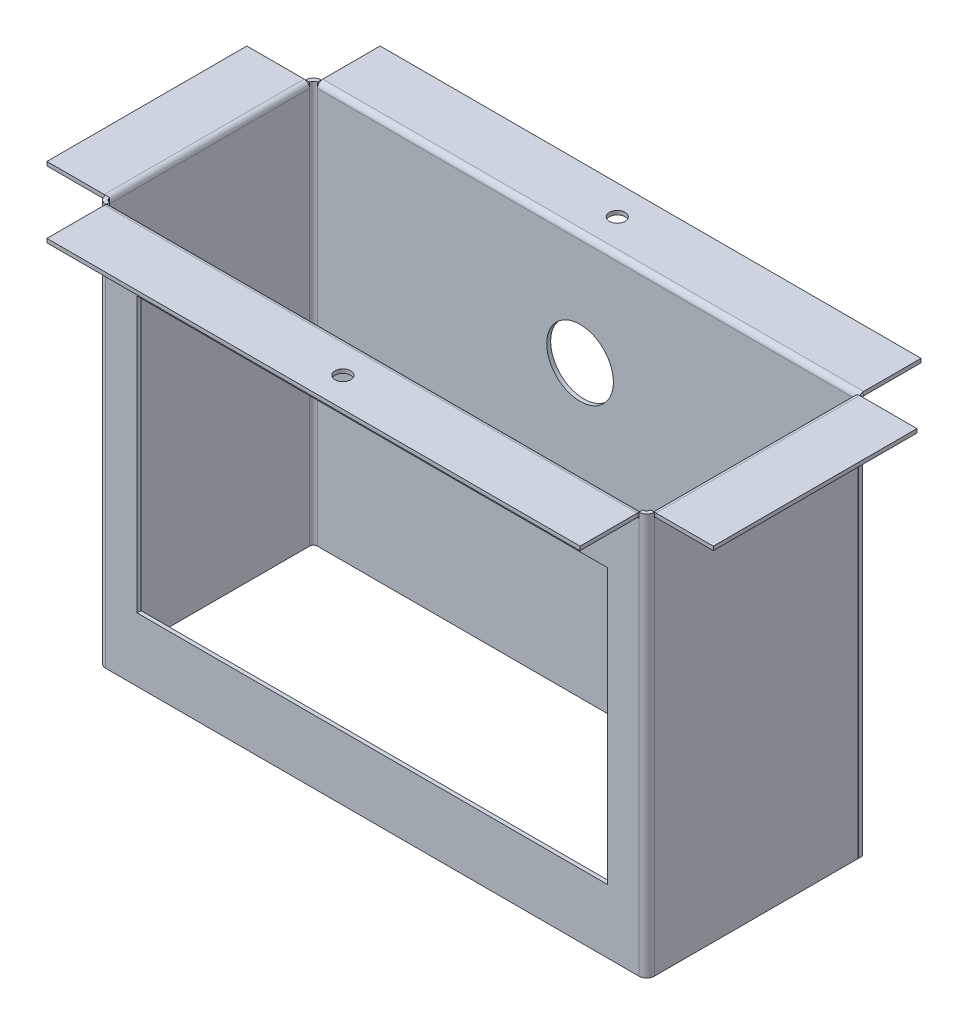
SolidWorks part; units mm, degrees
note: The reader was unsure of these and kept them because the rebuilt part matched: flange length of "Edge-Flange1", "Edge-Flange2", "Edge-Flange3", "Edge-Flange11".
material "Galvanized Steel"
ref_plane "Front Plane" through (0, 0, 0) normal (0, 0, 1) x (1, 0, 0)
ref_plane "Top Plane" through (0, 0, 0) normal (0, 1, 0) x (1, 0, 0)
ref_plane "Right Plane" through (0, 0, 0) normal (1, 0, 0) x (0, 0, -1)
sketch "Sketch1" plane through (0, 0, 0) normal (0, 0, 1) x (1, 0, 0)
  line L1 (44.0222, 46.0111) -> (-235.9778, 46.0111)
  line L2 (44.0222, 46.0111) -> (44.0222, -158.9889)
  line L3 (44.0222, -158.9889) -> (-235.9778, -158.9889)
  line L4 (-235.9778, 46.0111) -> (-235.9778, -158.9889)
  dimension "D1" = 205
  dimension "D2" = 280
base flange "Base-Flange1" sketch "Sketch1" thickness 2 reverse thickness direction no parameters "D1"=0.7366
edge flange "Edge-Flange1" sketch "Sketch8" flange angle 90 flange length 110 flange position material inside bend radius 2 thickness 2 relief obround parameters "D6"=10
sketch "Sketch8" plane through (-235.9778, 0, 0) normal (1, 0, 0) x (0, 1, 0)
  line L2 (-158.9889, 0) -> (-158.9889, 108)
  line L3 (-158.9889, 108) -> (46.0111, 108)
  line L4 (46.0111, 108) -> (46.0111, 0)
  line L6 (46.0111, 0) -> (-158.9889, 0) construction
  line L7 (46.0111, 0) -> (-158.9889, 0)
bend "EdgeBend1" bend radius 2 bend angle 90 parameters "D5"=1
edge flange "Edge-Flange2" sketch "Sketch11" flange angle 90 flange length 280 flange position material inside bend radius 2 thickness 2 relief obround parameters "D6"=10
sketch "Sketch11" plane through (-233.9778, 0, 108) normal (0, 0, -1) x (0, 1, 0)
  line L1 (46.0111, 0) -> (-158.9889, 0) construction
  line L2 (-158.9889, 0) -> (-158.9889, 278)
  line L3 (-158.9889, 278) -> (46.0111, 278)
  line L4 (46.0111, 278) -> (46.0111, 0)
  line L5 (46.0111, 0) -> (-158.9889, 0)
bend "EdgeBend2" bend radius 2 bend angle 90 parameters "D5"=2
edge flange "Edge-Flange3" sketch "Sketch14" flange angle 90 flange length 107.9 flange position material inside bend radius 2 thickness 2 relief obround parameters "D6"=10
sketch "Sketch14" plane through (44.0222, 0, 106) normal (-1, 0, 0) x (0, 1, 0)
  line L1 (46.0111, 0) -> (-158.9889, 0) construction
  line L2 (-158.9889, 0) -> (-158.9889, 105.9)
  line L3 (-158.9889, 105.9) -> (46.0111, 105.9)
  line L4 (46.0111, 105.9) -> (46.0111, 0)
  line L5 (46.0111, 0) -> (-158.9889, 0)
bend "EdgeBend3" bend radius 2 bend angle 90 parameters "D5"=3
sketch "Sketch15" plane through (0, 0, 108) normal (0, 0, 1) x (1, 0, 0)
  line L0 (-231.9778, 46.0111) -> (40.0222, 46.0111) construction
  line L1 (24.0222, 13.5111) -> (-215.9778, 13.5111)
  line L2 (24.0222, 13.5111) -> (24.0222, -126.4889)
  line L3 (24.0222, -126.4889) -> (-215.9778, -126.4889)
  line L4 (-215.9778, 13.5111) -> (-215.9778, -126.4889)
  line L5 (-235.9778, -158.9889) -> (-235.9778, 46.0111) construction
  dimension "D1" = 140
  dimension "D2" = 240
  dimension "D3" = 32.5
  dimension "D4" = 20
extrude "Cut-Extrude1" cut sketch "Sketch15" against normal blind 10 normal cut yes
sketch "Sketch16" plane through (0, 0, -2) normal (0, 0, -1) x (-1, 0, 0)
  line L1 (-44.0222, 46.0111) -> (231.9778, 46.0111) construction
  circle A0 centre (97.9778, -10.9889) radius 17
  dimension "D1" = 34
  dimension "D2" = 57
extrude "Cut-Extrude2" cut sketch "Sketch16" against normal blind 10 normal cut yes
edge flange "Edge-Flange11" sketch "Sketch50" flange profiles "Sketch50", "Sketch51", "Sketch52", "Sketch53" flange angle 90 flange length 32 flange position material inside bend radius 0.7366 thickness 2 relief none parameters "D6"=10, "D8"=1
sketch "Sketch50" plane through (0, 46.0111, -2) normal (0, 1, 0) x (1, 0, 0)
  line L2 (-231.9778, 0) -> (-231.9778, 30)
  line L3 (-231.9778, 30) -> (44.0222, 30)
  line L4 (44.0222, 30) -> (44.0222, 0)
  line L5 (44.0222, 0) -> (-231.9778, 0) construction
  line L6 (44.0222, 0) -> (-231.9778, 0)
sketch "Sketch51" plane through (-235.9778, 46.0111, 0) normal (0, 1, 0) x (0, 0, -1)
  line L0 (-2, 0) -> (-104, 0) construction
  line L1 (-2, 0) -> (-104, 0)
  line L2 (-104, 0) -> (-104, 30)
  line L3 (-104, 30) -> (-2, 30)
  line L4 (-2, 30) -> (-2, 0)
sketch "Sketch52" plane through (0, 46.0111, 108) normal (0, 1, 0) x (-1, 0, 0)
  line L0 (231.9778, 0) -> (-40.0222, 0) construction
  line L1 (231.9778, 0) -> (-40.0222, 0)
  line L2 (-40.0222, 0) -> (-40.0222, 30)
  line L3 (-40.0222, 30) -> (231.9778, 30)
  line L4 (231.9778, 30) -> (231.9778, 0)
sketch "Sketch53" plane through (44.0222, 46.0111, 0) normal (0, 1, 0) x (0, 0, 1)
  line L0 (104, 0) -> (0.1, 0) construction
  line L1 (104, 0) -> (0.1, 0)
  line L2 (0.1, 0) -> (0.1, 30)
  line L3 (0.1, 30) -> (104, 30)
  line L4 (104, 30) -> (104, 0)
bend "EdgeBend14" bend radius 0.7366 bend angle 90 parameters "D5"=10
bend "EdgeBend15" bend radius 0.7366 bend angle 90 parameters "D5"=11
bend "EdgeBend16" bend radius 0.7366 bend angle 90 parameters "D5"=12
bend "EdgeBend17" bend radius 0.7366 bend angle 90 parameters "D5"=13
sketch "Sketch55" plane through (0, 44.0111, 0) normal (0, -1, 0) x (1, 0, 0)
  line L0 (-265.9778, 2) -> (-265.9778, 104) construction
  line L1 (44.0222, -32) -> (-231.9778, -32) construction
  line L2 (-231.9778, 138) -> (40.0222, 138) construction
  circle A0 centre (-95.9778, -17) radius 4
  circle A1 centre (-95.9778, 123) radius 4
  dimension "D1" = 8
  dimension "D2" = 170
  dimension "D3" = 15
  dimension "D4" = 8
  dimension "D5" = 170
  dimension "D6" = 15
extrude "Cut-Extrude3" cut sketch "Sketch55" against normal blind 10 normal cut yes
sketch "Bend-Lines1" [suppressed] plane through (0, 0, 0) normal (0, 1, 0) x (1, 0, 0)
sketch "Bounding-Box1" [suppressed] plane through (0, 0, 0) normal (0, 1, 0) x (1, 0, 0)
sheet metal parameters "Sheet-Metal1" thickness 2 parameters "D1"=0.7366
flat pattern "Flat-Pattern1" [suppressed]
sketch "Bend-Lines2" plane through (0, 0, 0) normal (0, 1, 0) x (1, 0, 0)
sketch3d "Bounding-Box2" [suppressed]
  line L0 (235.9778, -158.9889, 0) -> (-40.0222, -158.9889, 0) construction
  line L1 (235.9778, 46.0111, 0) -> (-40.0222, 46.0111, 0) construction
  line L2 (235.9778, -158.9889, 0) -> (235.9778, 46.0111, 0) construction
  line L3 (-40.0222, -158.9889, 0) -> (-40.0222, 46.0111, 0) construction
sheet metal parameters "Sheet-Metal2" thickness 2 parameters "D1"=0.7366
flat pattern "Flat-Pattern1"
sketch "Bend-Lines2" plane through (0, 0, 0) normal (0, 0, 1) x (1, 0, 0)
  line L0 (-234.6051, 46.0111) -> (-234.6051, -158.9889) construction
  line L1 (-234.6051, 46.0111) -> (-234.6051, -158.9889) construction
sketch3d "Bounding-Box2" [suppressed]
  line L0 (-344.2324, -158.9889, 0) -> (40.0222, -158.9889, 0) construction
  line L1 (-344.2324, 46.0111, 0) -> (40.0222, 46.0111, 0) construction
  line L2 (-344.2324, -158.9889, 0) -> (-344.2324, 46.0111, 0) construction
  line L3 (40.0222, -158.9889, 0) -> (40.0222, 46.0111, 0) construction
bend of the flat pattern "Flatten-<EdgeBend1>1"
sheet metal parameters "Sheet-Metal3" thickness 2 parameters "D1"=0.7366
flat pattern "Flat-Pattern1"
sketch "Bend-Lines2" plane through (0, 0, 0) normal (0, 0, 1) x (1, 0, 0)
  line L0 (-234.6051, 46.0111) -> (-234.6051, -158.9889) construction
  line L1 (-234.6051, 46.0111) -> (-234.6051, -158.9889) construction
  line L2 (-342.8597, 46.0111) -> (-342.8597, -158.9889) construction
  line L3 (-342.8597, 46.0111) -> (-342.8597, -158.9889) construction
sketch3d "Bounding-Box2" [suppressed]
  line L0 (-617.4871, -158.9889, 0) -> (40.0222, -158.9889, 0) construction
  line L1 (-617.4871, 46.0111, 0) -> (40.0222, 46.0111, 0) construction
  line L2 (-617.4871, -158.9889, 0) -> (-617.4871, 46.0111, 0) construction
  line L3 (40.0222, -158.9889, 0) -> (40.0222, 46.0111, 0) construction
bend of the flat pattern "Flatten-<EdgeBend1>1"
bend of the flat pattern "Flatten-<EdgeBend2>1"
sheet metal parameters "Sheet-Metal4" thickness 2 parameters "D1"=0.7366
flat pattern "Flat-Pattern1"
sketch "Bend-Lines2" plane through (0, 0, 0) normal (0, 0, 1) x (1, 0, 0)
  line L0 (-234.6051, 46.0111) -> (-234.6051, -158.9889) construction
  line L1 (-234.6051, 46.0111) -> (-234.6051, -158.9889) construction
  line L2 (-342.8597, 46.0111) -> (-342.8597, -158.9889) construction
  line L3 (-342.8597, 46.0111) -> (-342.8597, -158.9889) construction
  line L4 (-616.1144, 46.0111) -> (-616.1144, -158.9889) construction
  line L5 (-616.1144, 46.0111) -> (-616.1144, -158.9889) construction
sketch3d "Bounding-Box2" [suppressed]
  line L0 (-722.7417, -158.9889, 0) -> (40.0222, -158.9889, 0) construction
  line L1 (-722.7417, 46.0111, 0) -> (40.0222, 46.0111, 0) construction
  line L2 (-722.7417, -158.9889, 0) -> (-722.7417, 46.0111, 0) construction
  line L3 (40.0222, -158.9889, 0) -> (40.0222, 46.0111, 0) construction
bend of the flat pattern "Flatten-<EdgeBend1>1"
bend of the flat pattern "Flatten-<EdgeBend2>1"
bend of the flat pattern "Flatten-<EdgeBend3>1"
sheet metal parameters "Sheet-Metal5" thickness 2 parameters "D1"=0.7366
flat pattern "Flat-Pattern1"
sketch "Bend-Lines2" plane through (0, 0, 0) normal (0, 0, 1) x (1, 0, 0)
  line L0 (-234.6051, 46.0111) -> (-234.6051, -158.9889) construction
  line L1 (-234.6051, 46.0111) -> (-234.6051, -158.9889) construction
  line L2 (-342.8597, 46.0111) -> (-342.8597, -158.9889) construction
  line L3 (-342.8597, 46.0111) -> (-342.8597, -158.9889) construction
  line L4 (-616.1144, 46.0111) -> (-616.1144, -158.9889) construction
  line L5 (-616.1144, 46.0111) -> (-616.1144, -158.9889) construction
sketch3d "Bounding-Box2" [suppressed]
  line L0 (-722.7417, -158.9889, 0) -> (40.0222, -158.9889, 0) construction
  line L1 (-722.7417, 46.0111, 0) -> (40.0222, 46.0111, 0) construction
  line L2 (-722.7417, -158.9889, 0) -> (-722.7417, 46.0111, 0) construction
  line L3 (40.0222, -158.9889, 0) -> (40.0222, 46.0111, 0) construction
bend of the flat pattern "Flatten-<EdgeBend1>1"
bend of the flat pattern "Flatten-<EdgeBend2>1"
bend of the flat pattern "Flatten-<EdgeBend3>1"
sheet metal parameters "Sheet-Metal6" thickness 2 parameters "D1"=0.7366
flat pattern "Flat-Pattern1"
sketch "Bend-Lines2" plane through (0, 0, 0) normal (0, 0, 1) x (1, 0, 0)
  line L0 (-234.2267, 46.0111) -> (-234.2267, -158.9889) construction
  line L1 (-234.2267, 46.0111) -> (-234.2267, -158.9889) construction
  line L2 (-341.7245, 46.0111) -> (-341.7245, -158.9889) construction
  line L3 (-341.7245, 46.0111) -> (-341.7245, -158.9889) construction
  line L4 (-614.2222, 46.0111) -> (-614.2222, -158.9889) construction
  line L5 (-614.2222, 46.0111) -> (-614.2222, -158.9889) construction
sketch3d "Bounding-Box2" [suppressed]
  line L0 (-720.4711, -158.9889, 0) -> (40.0222, -158.9889, 0) construction
  line L1 (-720.4711, 46.0111, 0) -> (40.0222, 46.0111, 0) construction
  line L2 (-720.4711, -158.9889, 0) -> (-720.4711, 46.0111, 0) construction
  line L3 (40.0222, -158.9889, 0) -> (40.0222, 46.0111, 0) construction
bend of the flat pattern "Flatten-<EdgeBend1>1"
bend of the flat pattern "Flatten-<EdgeBend2>1"
bend of the flat pattern "Flatten-<EdgeBend3>1"
sheet metal parameters "Sheet-Metal24" thickness 2 parameters "D1"=0.7366
flat pattern "Flat-Pattern1"
sketch "Bend-Lines2" plane through (0, 0, 0) normal (0, 0, 1) x (1, 0, 0)
  line L0 (-234.334, 46.0111) -> (-234.334, -158.9889) construction
  line L1 (-234.334, 46.0111) -> (-234.334, -158.9889) construction
  line L2 (-341.0464, 46.0111) -> (-341.0464, -158.9889) construction
  line L3 (-341.0464, 46.0111) -> (-341.0464, -158.9889) construction
  line L4 (-617.7588, 46.0111) -> (-617.7588, -158.9889) construction
  line L5 (-617.7588, 46.0111) -> (-617.7588, -158.9889) construction
  line L14 (-620.1149, 44.6384) -> (-724.0149, 44.6384) construction
  line L15 (-343.4026, 44.6384) -> (-615.4026, 44.6384) construction
  line L16 (-236.6902, 44.6384) -> (-338.6902, 44.6384) construction
  line L17 (44.0222, 44.6384) -> (-231.9778, 44.6384) construction
  line L18 (-620.1149, 44.6384) -> (-724.0149, 44.6384) construction
  line L19 (-343.4026, 44.6384) -> (-615.4026, 44.6384) construction
  line L20 (-236.6902, 44.6384) -> (-338.6902, 44.6384) construction
  line L21 (44.0222, 44.6384) -> (-231.9778, 44.6384) construction
  point P8 (-338.6902, -156.9159)
  point P9 (-236.6902, -156.9159)
  point P10 (-724.0149, -156.9159)
  point P11 (-620.1149, -156.9159)
  point P12 (-231.9778, -156.9159)
  point P13 (44.0222, -156.9159)
  point P14 (-615.4026, -156.9159)
  point P15 (-343.4026, -156.9159)
sketch3d "Bounding-Box2" [suppressed]
  line L0 (-724.0149, -158.9889, 0) -> (44.0222, -158.9889, 0) construction
  line L1 (-724.0149, 75.2658, 0) -> (44.0222, 75.2658, 0) construction
  line L2 (-724.0149, -158.9889, 0) -> (-724.0149, 75.2658, 0) construction
  line L3 (44.0222, -158.9889, 0) -> (44.0222, 75.2658, 0) construction
bend of the flat pattern "Flatten-<EdgeBend1>1"
bend of the flat pattern "Flatten-<EdgeBend2>1"
bend of the flat pattern "Flatten-<EdgeBend3>1"
bend of the flat pattern "Flatten-<EdgeBend14>1"
bend of the flat pattern "Flatten-<EdgeBend15>1"
bend of the flat pattern "Flatten-<EdgeBend16>1"
bend of the flat pattern "Flatten-<EdgeBend17>1"
sheet metal parameters "Sheet-Metal26" thickness 2 parameters "D1"=0.7366
flat pattern "Flat-Pattern1"
sketch "Bend-Lines2" plane through (0, 0, 0) normal (0, 0, 1) x (1, 0, 0)
  line L0 (-234.334, 46.0111) -> (-234.334, -158.9889) construction
  line L1 (-234.334, 46.0111) -> (-234.334, -158.9889) construction
  line L2 (-341.0464, 46.0111) -> (-341.0464, -158.9889) construction
  line L3 (-341.0464, 46.0111) -> (-341.0464, -158.9889) construction
  line L4 (-617.7588, 46.0111) -> (-617.7588, -158.9889) construction
  line L5 (-617.7588, 46.0111) -> (-617.7588, -158.9889) construction
  line L14 (-620.1149, 44.6384) -> (-724.0149, 44.6384) construction
  line L15 (-343.4026, 44.6384) -> (-615.4026, 44.6384) construction
  line L16 (-236.6902, 44.6384) -> (-338.6902, 44.6384) construction
  line L17 (44.0222, 44.6384) -> (-231.9778, 44.6384) construction
  line L18 (-620.1149, 44.6384) -> (-724.0149, 44.6384) construction
  line L19 (-343.4026, 44.6384) -> (-615.4026, 44.6384) construction
  line L20 (-236.6902, 44.6384) -> (-338.6902, 44.6384) construction
  line L21 (44.0222, 44.6384) -> (-231.9778, 44.6384) construction
sketch3d "Bounding-Box2" [suppressed]
  line L0 (-724.0149, -158.9889, 0) -> (44.0222, -158.9889, 0) construction
  line L1 (-724.0149, 75.2658, 0) -> (44.0222, 75.2658, 0) construction
  line L2 (-724.0149, -158.9889, 0) -> (-724.0149, 75.2658, 0) construction
  line L3 (44.0222, -158.9889, 0) -> (44.0222, 75.2658, 0) construction
bend of the flat pattern "Flatten-<EdgeBend1>1"
bend of the flat pattern "Flatten-<EdgeBend2>1"
bend of the flat pattern "Flatten-<EdgeBend3>1"
bend of the flat pattern "Flatten-<EdgeBend14>1"
bend of the flat pattern "Flatten-<EdgeBend15>1"
bend of the flat pattern "Flatten-<EdgeBend16>1"
bend of the flat pattern "Flatten-<EdgeBend17>1"
